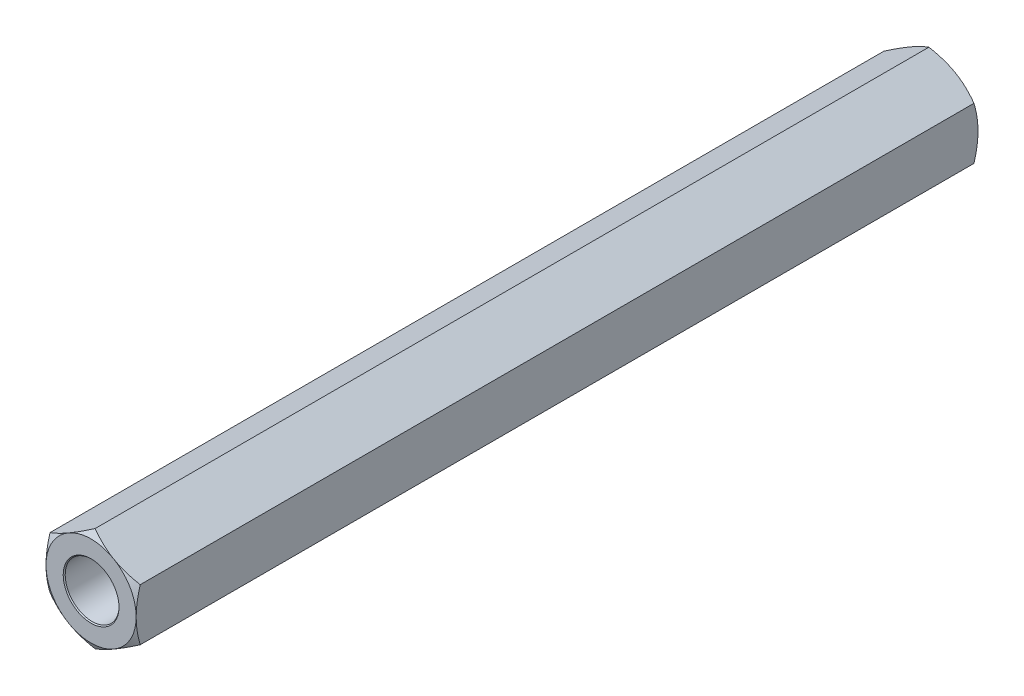
SolidWorks part; units mm, degrees
ref_plane "Front Plane" through (0, 0, 0) normal (0, 0, 1) x (1, 0, 0)
ref_plane "Top Plane" through (0, 0, 0) normal (0, 1, 0) x (1, 0, 0)
ref_plane "Right Plane" through (0, 0, 0) normal (1, 0, 0) x (0, 0, -1)
sketch "Sketch3" plane through (0, 0, 0) normal (1, 0, 0) x (0, 0, -1)
  line L0 (-22.225, 0) -> (22.225, 0) construction
  line L1 (0, 2.3813) -> (0, -2.3813) construction
  line L2 (-22.225, 1.4224) -> (-22.225, -1.4224) construction
  point P2 (15.875, 0)
  point P3 (-15.875, 0)
  dimension "D1" = 6.35
  dimension "Length" = 44.45
  dimension "Min Thread Length" = 6.35
  dimension "Thread Dia" = 2.8448
  dimension "Hex" = 4.7625
sketch "Sketch1" plane through (0, 0, 0) normal (0, 0, 1) x (1, 0, 0)
  line L1 (0, 2.7496) -> (-2.3813, 1.3748)
  line L2 (-2.3813, 1.3748) -> (-2.3813, -1.3748)
  line L3 (-2.3813, -1.3748) -> (0, -2.7496)
  line L4 (0, -2.7496) -> (2.3813, -1.3748)
  line L5 (2.3813, -1.3748) -> (2.3813, 1.3748)
  line L6 (2.3813, 1.3748) -> (0, 2.7496)
  circle A0 centre (0, 0) radius 2.3813 construction
  circle A1 centre (0, 0) radius 1.4224
extrude "Extrude1" add sketch "Sketch1" along normal up to vertex (22.225 mm away) and the other way up to vertex (22.225 mm away) up to point (0, 0, 22.225) other way up to point (0, 0, -22.225)
sketch "Sketch11" plane through (0, 0, -22.225) normal (0, 0, -1) x (-1, 0, 0)
  circle A0 centre (0, 0) radius 1.4224 construction
  circle A1 centre (0, 0) radius 1.4224
curve "Helix/Spiral1" pitch 0.635 height 45.085 turns 71 parameters "Pitch"=0.635
sketch "Sketch12" plane through (0, 0, 0) normal (1, 0, 0) x (0, 0, -1)
  line L0 (22.7806, 1.4224) -> (22.225, 1.4224)
  line L1 (22.7806, 1.4224) -> (22.5425, 1.01)
  line L2 (22.5425, 1.01) -> (22.4631, 1.01)
  line L3 (22.4631, 1.01) -> (22.225, 1.4224)
  line L4 (22.5028, 1.01) -> (22.5028, 1.4224) construction
  line L5 (22.6616, 1.2162) -> (22.3441, 1.2162) construction
  dimension "D1" = 0.0794
  dimension "D2" = 0.3175
  dimension "D3" = 60
sweep "Sweep1" [suppressed] add profiles "Sketch12" path "Helix/Spiral1"
sketch "Sketch6" plane through (0, 0, -22.225) normal (0, 0, -1) x (-1, 0, 0)
  line L6 (0, 2.7496) -> (-2.3813, 1.3748)
  line L7 (-2.3813, 1.3748) -> (-2.3813, -1.3748)
  line L8 (-2.3813, -1.3748) -> (0, -2.7496)
  line L9 (0, -2.7496) -> (2.3813, -1.3748)
  line L10 (2.3813, -1.3748) -> (2.3813, 1.3748)
  line L11 (2.3813, 1.3748) -> (0, 2.7496)
  line L12 (0, 2.7496) -> (-2.3813, 1.3748)
  line L13 (-2.3813, 1.3748) -> (-2.3813, -1.3748)
  line L14 (-2.3813, -1.3748) -> (0, -2.7496)
  line L15 (0, -2.7496) -> (2.3813, -1.3748)
  line L16 (2.3813, -1.3748) -> (2.3813, 1.3748)
  line L17 (2.3813, 1.3748) -> (0, 2.7496)
  dimension "D1" = 0
extrude "Extrude2" [suppressed] cut sketch "Sketch6" along normal through all
sketch "Sketch7" plane through (0, 0, -22.225) normal (0, 0, -1) x (-1, 0, 0)
  circle A2 centre (0, 0) radius 1.4732
  circle A3 centre (0, 0) radius 1.4732
  dimension "D1" = 0.0508
extrude "Extrude3" cut sketch "Sketch7" against normal through all draft 43
sketch "Sketch8" plane through (0, 0, -22.225) normal (0, 0, -1) x (-1, 0, 0)
  circle A0 centre (0, 0) radius 2.3813 construction
  circle A1 centre (0, 0) radius 2.3813
extrude "Extrude4" cut sketch "Sketch8" against normal through all draft 60 flip side to cut
mirror "Mirror1" about plane through (0, 0, 0) normal (0, 0, 1) of "Extrude2", "Extrude3", "Extrude4"
sketch "Sketch9" [suppressed] plane through (0, 0, 0) normal (1, 0, 0) x (0, 0, -1)
  line L1 (-15.875, 1.4732) -> (15.875, 1.4732)
  line L2 (-15.875, 1.4732) -> (-15.875, 0)
  line L3 (-15.875, 0) -> (15.875, 0)
  line L4 (15.875, 1.4732) -> (15.875, 0)
  line L7 (-22.225, 0) -> (22.225, 0) construction
revolve "Revolve" [suppressed] add sketch "Sketch9" angle 360 about L0
sketch "Sketch10" [suppressed] plane through (0, 0, 0) normal (1, 0, 0) x (0, 0, -1)
  line L0 (22.225, 1.4224) -> (15.875, 1.4224)
  line L1 (-22.225, 1.4224) -> (-15.875, 1.4224)
  line L2 (15.875, 1.4224) -> (15.875, -1.4224)
  line L3 (-22.225, -1.4732) -> (-15.875, -1.4732)
  line L4 (-15.875, 1.4224) -> (-15.875, -1.4732)
  line L5 (15.875, -1.4224) -> (22.225, -1.4224)
equation "\"D1@Sketch3\" = \"Min Thread Length@Sketch3\""
equation "\"D3@Helix/Spiral1\" = \"Length@Sketch3\"+\"Pitch@Helix/Spiral1\""
equation "\"D1@Sketch12\" = \"Pitch@Helix/Spiral1\"*.125"
equation "\"D2@Sketch12\" = \"Pitch@Helix/Spiral1\"*.5"
